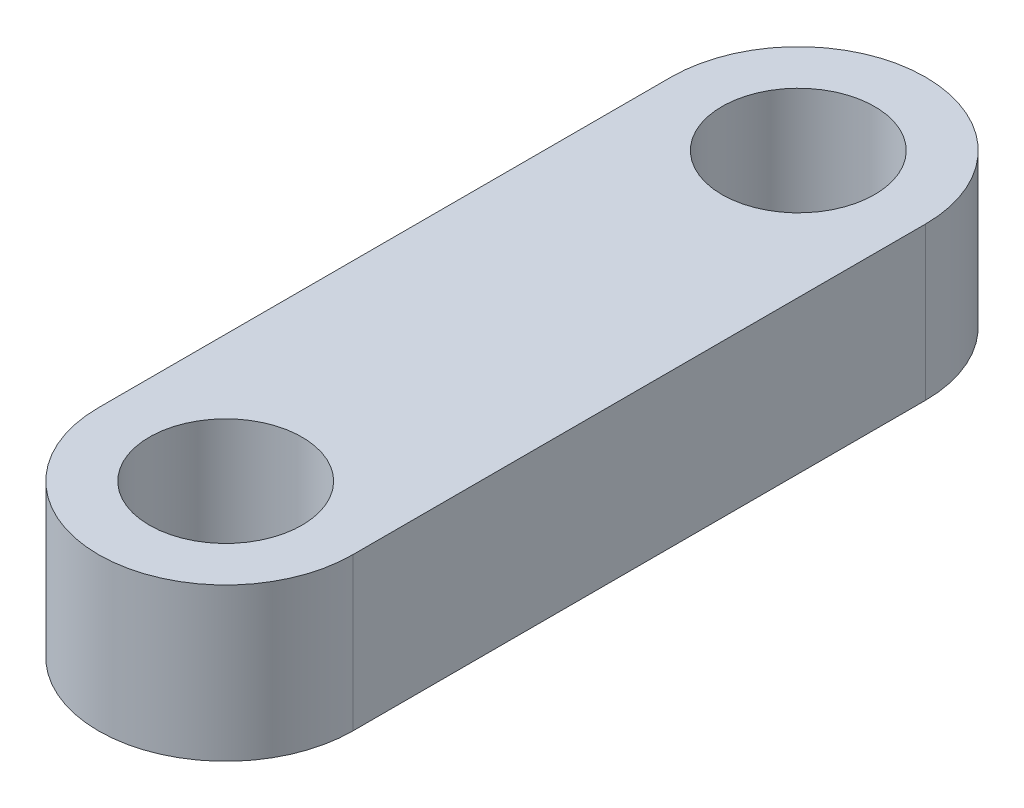
SolidWorks part; units mm, degrees
ref_plane "Front Plane" through (0, 0, 0) normal (0, 0, 1) x (1, 0, 0)
ref_plane "Top Plane" through (0, 0, 0) normal (0, 1, 0) x (1, 0, 0)
ref_plane "Right Plane" through (0, 0, 0) normal (1, 0, 0) x (0, 0, -1)
sketch "Sketch1" plane through (0, 0, 0) normal (0, 1, 0) x (1, 0, 0)
  line L0 (0, -11.25) -> (0, 11.25) construction
  line L1 (0, 0) -> (50000, 0) construction
  line L2 (-5, -11.25) -> (-5, 11.25)
  line L3 (5, -11.25) -> (5, 11.25)
  circle A0 centre (0, 11.25) radius 3
  circle A1 centre (0, 11.25) radius 5
  circle A2 centre (0, -11.25) radius 5
  circle A3 centre (0, -11.25) radius 3
  point P3 (-1, 6.351)
  point P4 (0, 0)
  point P12 (-5, 11.25)
  point P16 (5, 0)
  point P17 (-5, 0)
  dimension "D3" = 6
  dimension "D1" = 22.5
  dimension "D2" = 2
extrude "Boss-Extrude1" add sketch "Sketch1" along normal blind 6 contours A1 A0 | L2 A2 L3 A1 | A2 A3 region at (0, 0, 0) region at (0, 0, 6.3914) region at (0, 0, -16.1086)
